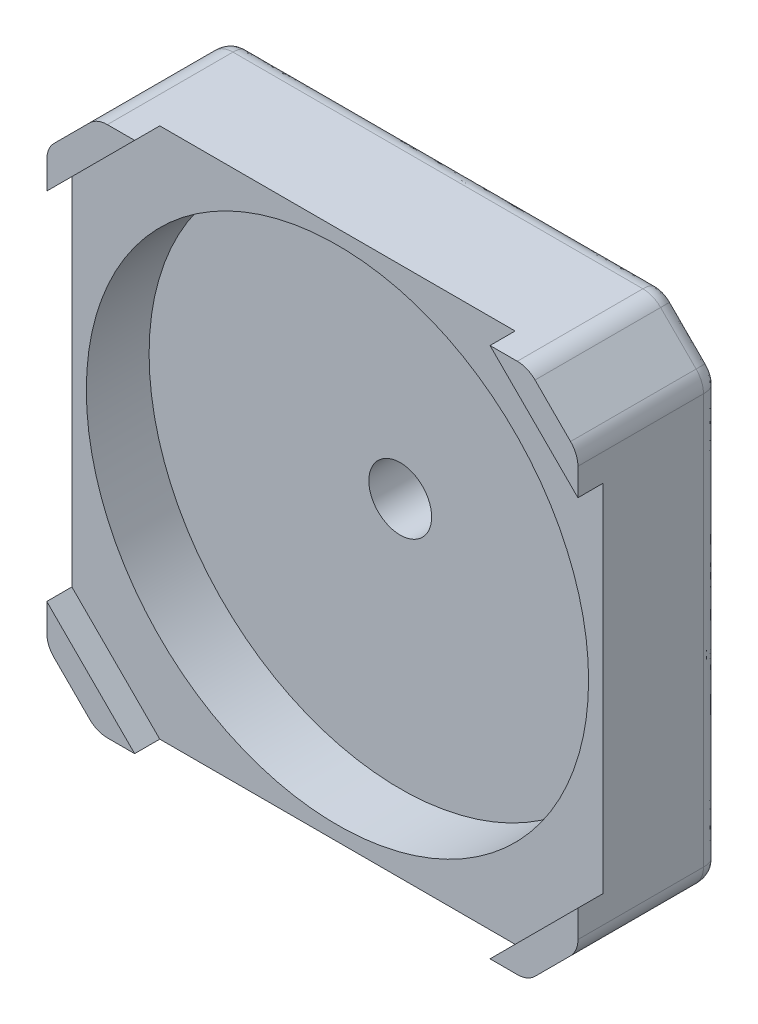
SolidWorks part; units mm, degrees
material "201 Stal nierdzewna odprężona (SS)"
ref_plane "Płaszczyzna przednia" through (0, 0, 0) normal (0, 0, 1) x (1, 0, 0)
ref_plane "Płaszczyzna górna" through (0, 0, 0) normal (0, 1, 0) x (1, 0, 0)
ref_plane "Płaszczyzna prawa" through (0, 0, 0) normal (1, 0, 0) x (0, 0, -1)
sketch "Szkic1" plane through (0, 0, 0) normal (0, 0, 1) x (1, 0, 0)
  line L1 (-21.15, -21.15) -> (21.15, -21.15)
  line L2 (-21.15, -21.15) -> (-21.15, 21.15)
  line L3 (-21.15, 21.15) -> (21.15, 21.15)
  line L4 (21.15, -21.15) -> (21.15, 21.15)
  line L5 (0, 21.15) -> (0, -21.15) construction
  line L6 (-21.15, 0) -> (21.15, 0) construction
  point P0 (0, 0)
  dimension "D1" = 42.3
  dimension "D2" = 42.3
extrude "Dodanie-wyciągnięcie1" add sketch "Szkic1" along normal blind 9
chamfer "Sfazowanie1" distance 4 angle 45 4 edges at (-21.15, -21.15, 4.5) (21.15, -21.15, 4.5) (-21.15, 21.15, 4.5) (21.15, 21.15, 4.5)
fillet "Zaokrąglenie1" radius 2 8 edges at (17.15, -21.15, 4.5) (21.15, -17.15, 4.5) (21.15, 17.15, 4.5) (17.15, 21.15, 4.5) (-21.15, 17.15, 4.5) (-21.15, -17.15, 4.5) (-17.15, -21.15, 4.5) (-17.15, 21.15, 4.5)
fillet "Zaokrąglenie2" radius 0.5 16 edges at (0, -21.15, 0) (17.0869, -20.9978, 0) (-17.0869, -20.9978, 0) (19.15, -19.15, 0) (-19.15, -19.15, 0) (20.9978, -17.0869, 0) (-20.9978, -17.0869, 0) (21.15, 0, 0) (-21.15, 0, 0) (20.9978, 17.0869, 0) (-20.9978, 17.0869, 0) (19.15, 19.15, 0) (-19.15, 19.15, 0) (17.0869, 20.9978, 0) (-17.0869, 20.9978, 0) (0, 21.15, 0) second distance 1 first distance on face at (0, 0, 0)
sketch "Szkic2" plane through (0, 0, 0) normal (0, 0, -1) x (-1, 0, 0)
  circle A0 centre (0, 0) radius 11
  dimension "D1" = 22
extrude "Dodanie-wyciągnięcie2" add sketch "Szkic2" along normal blind 2
ref_axis "Oś1" through (0, 0, -2.55) along (0, 0, 1)
sketch "Szkic3" plane through (0, 0, 0) normal (0, 1, 0) x (1, 0, 0)
  line L0 (-11, 0) -> (-11.2, -0.15)
  line L1 (-11.2, -0.15) -> (-11.3, -0.15)
  line L2 (-11.3, -0.15) -> (-11.5, 0)
  line L3 (-16.3216, 0) -> (16.3216, 0) construction
  line L4 (-11.5, 0) -> (-11, 0)
  line L5 (-11.25, -0.15) -> (-11.25, 2.6586) construction
  dimension "D1" = 0.1
  dimension "D2" = 0.5
  dimension "D3" = 0.15
revolve "Wycięcie-obrót1" cut sketch "Szkic3" angle 360 about axis through (0, 0, -2.55) along (0, 0, 1)
sketch "Szkic4" plane through (0, 0, -2) normal (0, 0, -1) x (-1, 0, 0)
  circle A0 centre (0, 0) radius 3.75
  dimension "D1" = 7.5
extrude "Wytnij-wyciągnięcie1" cut sketch "Szkic4" against normal up to surface (2 mm away) up to face at (-11.5, 0, 0)
sketch "Szkic5" plane through (0, 0, 0) normal (0, 0, -1) x (-1, 0, 0)
  circle A0 centre (0, 0) radius 2.5
  dimension "D1" = 5
extrude "Wytnij-wyciągnięcie2" cut sketch "Szkic5" against normal up to next
sketch "Szkic6" plane through (0, 0, 9) normal (0, 0, 1) x (1, 0, 0)
  line L0 (14.15, 21.15) -> (21.15, 14.15)
  line L1 (16.3216, 21.15) -> (-16.3216, 21.15) construction
  line L2 (21.15, -16.3216) -> (21.15, 16.3216) construction
  line L3 (20.5642, 17.7358) -> (17.7358, 20.5642) construction
  line L4 (21.15, 14.15) -> (21.15, 21.15) construction
  line L5 (21.15, 21.15) -> (14.15, 21.15) construction
  line L14 (-16.3216, -21.15) -> (16.3216, -21.15)
  line L15 (17.7358, -20.5642) -> (20.5642, -17.7358)
  line L16 (21.15, -16.3216) -> (21.15, 16.3216)
  line L17 (20.5642, 17.7358) -> (17.7358, 20.5642)
  line L18 (16.3216, 21.15) -> (-16.3216, 21.15)
  line L19 (-17.7358, 20.5642) -> (-20.5642, 17.7358)
  line L20 (-21.15, 16.3216) -> (-21.15, -16.3216)
  line L21 (-20.5642, -17.7358) -> (-17.7358, -20.5642)
  line L24 (21.15, 14.15) -> (21.15, 16.3216)
  line L25 (20.5642, 17.7358) -> (17.7358, 20.5642)
  line L26 (16.3216, 21.15) -> (14.15, 21.15)
  arc A9 (16.3216, -21.15) -> (17.7358, -20.5642) centre (16.3216, -19.15) ccw
  arc A10 (20.5642, -17.7358) -> (21.15, -16.3216) centre (19.15, -16.3216) ccw
  arc A11 (21.15, 16.3216) -> (20.5642, 17.7358) centre (19.15, 16.3216) ccw
  arc A12 (17.7358, 20.5642) -> (16.3216, 21.15) centre (16.3216, 19.15) ccw
  arc A13 (-16.3216, 21.15) -> (-17.7358, 20.5642) centre (-16.3216, 19.15) ccw
  arc A14 (-20.5642, 17.7358) -> (-21.15, 16.3216) centre (-19.15, 16.3216) ccw
  arc A15 (-21.15, -16.3216) -> (-20.5642, -17.7358) centre (-19.15, -16.3216) ccw
  arc A16 (-17.7358, -20.5642) -> (-16.3216, -21.15) centre (-16.3216, -19.15) ccw
  arc A19 (21.15, 16.3216) -> (20.5642, 17.7358) centre (19.15, 16.3216) ccw
  arc A20 (17.7358, 20.5642) -> (16.3216, 21.15) centre (16.3216, 19.15) ccw
  dimension "D1" = 7
  dimension "D2" = 0
extrude "Dodanie-wyciągnięcie3" add sketch "Szkic6" along normal blind 2
pattern_circular "Szyk kołowy1" count 4 over 360 about axis through (0, 0, -2.55) along (0, 0, 1) of "Dodanie-wyciągnięcie3"
sketch "Szkic7" plane through (0, 0, 0) normal (0, 0, -1) x (-1, 0, 0)
  line L1 (-15.5, -15.5) -> (15.5, -15.5) construction
  line L2 (-15.5, -15.5) -> (-15.5, 15.5) construction
  line L3 (-15.5, 15.5) -> (15.5, 15.5) construction
  line L4 (15.5, -15.5) -> (15.5, 15.5) construction
  line L5 (0, 15.5) -> (0, -15.5) construction
  line L6 (-15.5, 0) -> (15.5, 0) construction
  point P0 (0, 0)
  dimension "D1" = 31
  dimension "D2" = 31
hole_wizard "Otwór gwintowany M31" positions "Szkic8" profile "Szkic9" tap size "M3" standard "ISO"
sketch "Szkic8" plane through (0, 0, 0) normal (0, 0, -1) x (-1, 0, 0)
  point P0 (-15.5, 15.5)
  point P3 (15.5, 15.5)
  point P6 (15.5, -15.5)
  point P9 (-15.5, -15.5)
cosmetic thread "Gwint otworu1" parameters "D1"=4, "D2"=3
cosmetic thread "Gwint otworu2" parameters "D1"=4, "D2"=3
cosmetic thread "Gwint otworu3" parameters "D1"=4, "D2"=3
cosmetic thread "Gwint otworu4" parameters "D1"=4, "D2"=3
sketch "Szkic9" plane through (15.5, 15.5, 0) normal (1, 0, 0) x (0, 1, 0)
  line L0 (0, 0) -> (0, 5.2511)
  line L1 (0, 5.2511) -> (1.25, 4.5)
  line L2 (1.25, 4.5) -> (1.25, 0)
  line L5 (1.25, 0) -> (0, 0)
  line L10 (0, 5.2511) -> (-1.25, 4.5) construction
  line L11 (0, -6.35) -> (0, 107.95) construction
  dimension "Średnica wiertła gwintu" = 2.5
  dimension "Głębokość otworu gwintowanego" = 4.5
  dimension "Kąt wiertła" = 118
sketch "Szkic10" plane through (0, 0, 9) normal (0, 0, 1) x (1, 0, 0)
  circle A0 centre (0, 0) radius 20
  dimension "D1" = 40
extrude "Wytnij-wyciągnięcie3" cut sketch "Szkic10" against normal blind 5
